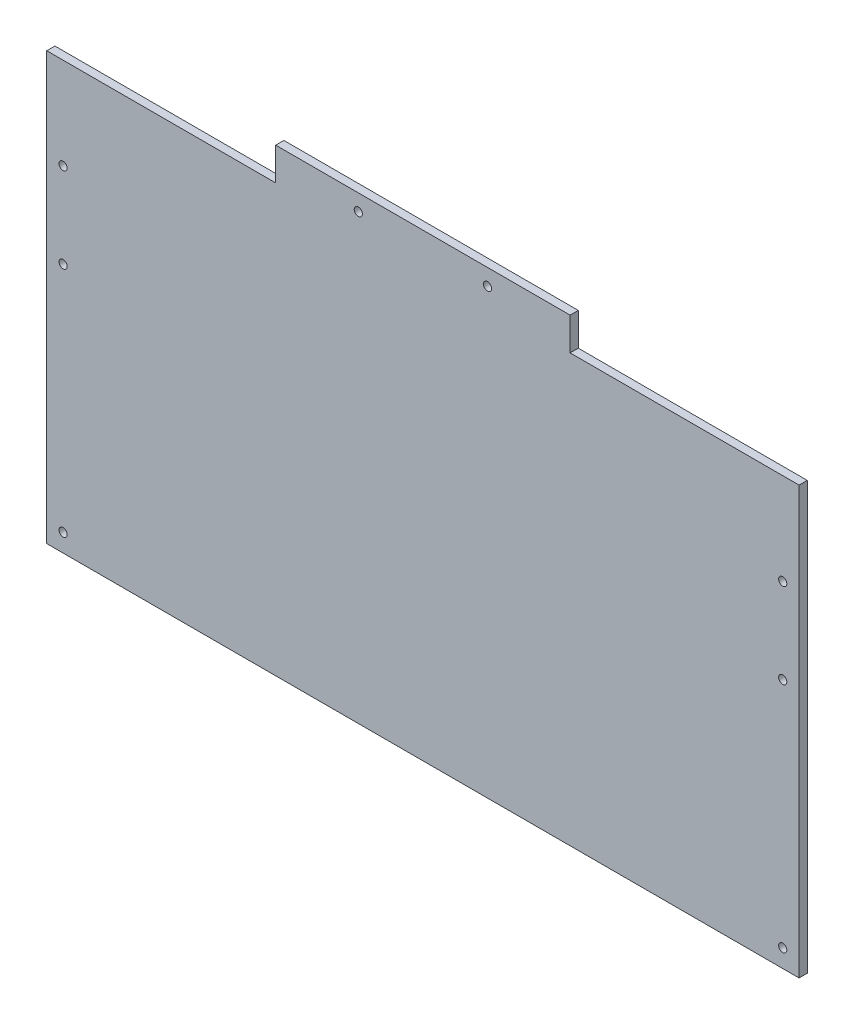
SolidWorks part; units mm, degrees
material "아크릴(내충격성)"
ref_plane "정면" through (0, 0, 0) normal (0, 0, 1) x (1, 0, 0)
ref_plane "윗면" through (0, 0, 0) normal (0, 1, 0) x (1, 0, 0)
ref_plane "우측면" through (0, 0, 0) normal (1, 0, 0) x (0, 0, -1)
sketch "스케치1" plane through (0, 0, 0) normal (0, 0, 1) x (1, 0, 0)
  line L1 (-230, 130.5) -> (230, 130.5)
  line L2 (-230, 130.5) -> (-230, -130.5)
  line L3 (-230, -130.5) -> (230, -130.5)
  line L4 (230, 130.5) -> (230, -130.5)
  line L5 (-230, 130.5) -> (230, -130.5) construction
  line L6 (-230, -130.5) -> (230, 130.5) construction
  point P0 (0, 0)
  dimension "D1" = 261
  dimension "D2" = 460
extrude "보스-돌출1" add sketch "스케치1" along normal blind 5
sketch "스케치2" plane through (0, 0, 5) normal (0, 0, 1) x (1, 0, 0)
  line L1 (-230, -130.5) -> (230, -130.5) construction
  line L2 (0, 78.4096) -> (0, -43.6333) construction
  line L5 (230, 130.5) -> (-230, 130.5) construction
  line L6 (220, 130.5) -> (220, -130.5) construction
  circle A3 centre (220, 74.5) radius 2.5
  circle A4 centre (220, 22.5) radius 2.5
  circle A5 centre (220, -119.5) radius 2.5
  circle A6 centre (-220, 74.5) radius 2.5
  circle A7 centre (-220, 22.5) radius 2.5
  circle A8 centre (-220, -119.5) radius 2.5
  dimension "D4" = 142
  dimension "56" = 56
  dimension "D5" = 52
extrude "컷-돌출1" cut sketch "스케치2" against normal through all contours A6 | A7 | A8 | A5 | A3 | A4
sketch "스케치3" plane through (0, 0, 5) normal (0, 0, 1) x (1, 0, 0)
  line L1 (230, 130.5) -> (-230, 130.5) construction
  line L2 (90, 130.5) -> (90, 150.5)
  line L4 (-90, 130.5) -> (-90, 150.5)
  line L5 (-90, 150.5) -> (90, 150.5)
  line L6 (-90, 130.5) -> (-90, 112.1074)
  line L7 (-90, 112.1074) -> (90, 112.1074)
  line L8 (90, 112.1074) -> (90, 130.5)
  circle A0 centre (-39.5, 140.5) radius 2.5
  circle A1 centre (39.5, 140.5) radius 2.5
extrude "보스-돌출2" add sketch "스케치3" against normal blind 5
